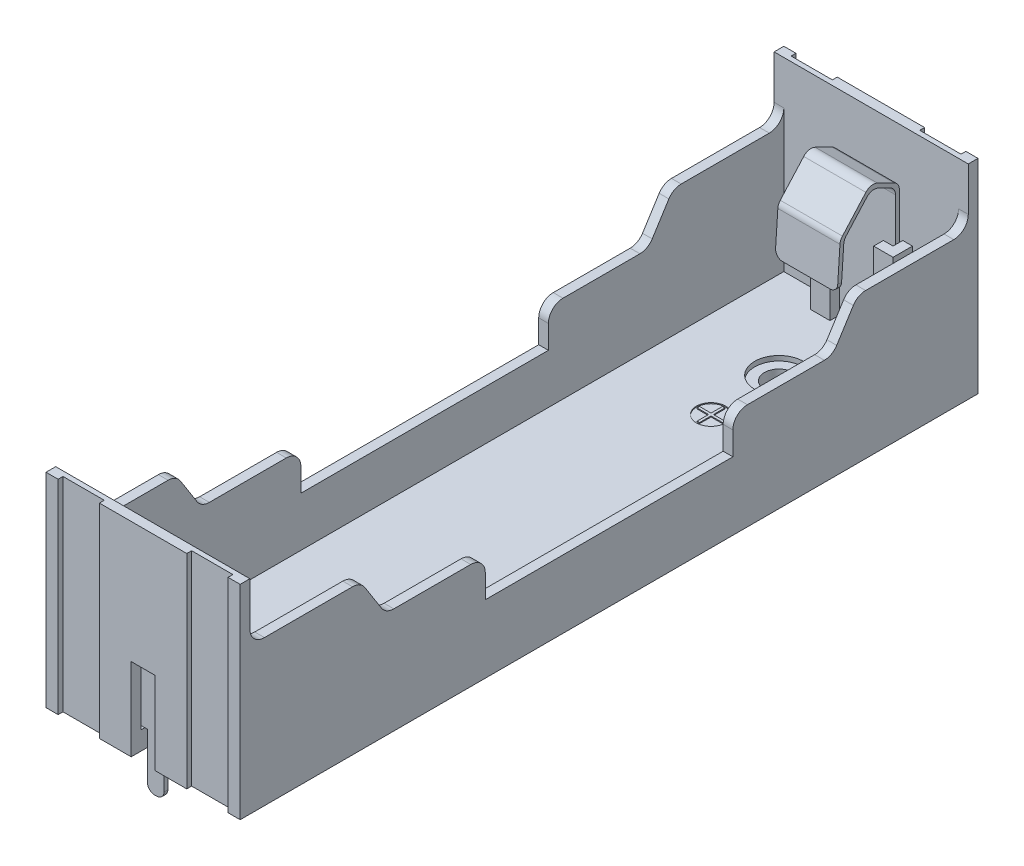
SolidWorks part; units mm, degrees
material "ABS"
ref_plane "Спереди" through (0, 0, 0) normal (0, 0, 1) x (1, 0, 0)
ref_plane "Сверху" through (0, 0, 0) normal (0, 1, 0) x (1, 0, 0)
ref_plane "Справа" through (0, 0, 0) normal (1, 0, 0) x (0, 0, -1)
other "Configuration Table"
sketch "Эскиз1" plane through (0, 0, 0) normal (0, 1, 0) x (1, 0, 0)
  line L1 (-10, 38) -> (10, 38)
  line L2 (-10, 38) -> (-10, -38)
  line L3 (-10, -38) -> (10, -38)
  line L4 (10, 38) -> (10, -38)
  line L5 (-10, 38) -> (10, -38) construction
  line L6 (-10, -38) -> (10, 38) construction
  point P0 (0, 0)
  dimension "D1" = 76
  dimension "D2" = 20
extrude "Основа" add sketch "Эскиз1" along normal blind 21
sketch "Эскиз2" plane through (0, 0, 0) normal (0, 1, 0) x (1, 0, 0)
  line L1 (10, 38) -> (-10, 38) construction
  line L2 (-4.5, 38) -> (-4.5, 37.5)
  line L3 (-4.5, 37.5) -> (-8.75, 37.5)
  line L4 (-8.75, 37.5) -> (-8.75, 38)
  line L5 (-8.75, 38) -> (-10.75, 38)
  line L6 (-10.75, 38) -> (-10.75, 37.5)
  line L13 (-10.75, 38) -> (-10, 38)
  line L14 (-10, 38) -> (-10, 46.5071)
  line L15 (-10, 46.5071) -> (10, 46.5071)
  line L16 (0, 46.5071) -> (0, 38)
  line L17 (4.5, 38) -> (-4.5, 38)
  line L18 (10, 38) -> (10, 46.5071)
  line L26 (10.75, 38) -> (10.75, 37.5)
  line L27 (8.75, 38) -> (10.75, 38)
  line L28 (4.5, 38) -> (4.5, 37.5)
  line L29 (4.5, 37.5) -> (8.75, 37.5)
  line L30 (8.75, 37.5) -> (8.75, 38)
  line L31 (10.75, 38) -> (10, 38)
  line L32 (-10.75, 37.5) -> (-8.75, 37.5)
  line L33 (10.75, 37.5) -> (8.75, 37.5)
  point P22 (0, 38)
  dimension "D1" = 9
  dimension "D2" = 2
  dimension "D3" = 4.25
  dimension "D4" = 0.5
extrude "Рёбра" cut sketch "Эскиз2" along normal through all contours L29 L30 L27 L26 L18 L15 L16 L17 L28 | L17 L16 L15 L14 L13 L6 L5 L4 L3 L2 region at (-5.0396, 0, -42.1438) region at (5.0396, 0, -42.1438)
mirror "Зеркальное отражение1" about plane through (0, 0, 0) normal (0, 0, 1) of "Рёбра"
sketch "Эскиз3" plane through (0, 21, 0) normal (0, 1, 0) x (1, 0, 0)
  line L0 (9, 0) -> (-9, 0) construction
  line L1 (9, 37) -> (-9, 37)
  line L2 (9, 37) -> (9, -37)
  line L3 (9, -37) -> (-9, -37)
  line L4 (-9, 37) -> (-9, -37)
  line L5 (9, 37) -> (-9, -37) construction
  line L6 (9, -37) -> (-9, 37) construction
  point P0 (0, 0)
  point P9 (0, 0)
  dimension "D1" = 18
  dimension "D2" = 74
extrude "Отсеки" cut sketch "Эскиз3" against normal blind 19.1
sketch "Эскиз4" plane through (0, 0, 0) normal (1, 0, 0) x (0, 0, -1)
  line L0 (37, 21) -> (-37, 21) construction
  line L1 (37, 27) -> (-37, 27)
  line L2 (37, 27) -> (37, 15)
  line L3 (37, 15) -> (-37, 15)
  line L4 (-37, 27) -> (-37, 15)
  line L5 (37, 27) -> (-37, 15) construction
  line L6 (37, 15) -> (-37, 27) construction
  line L7 (-37, 1.9) -> (-37, 21) construction
  point P0 (0, 21)
  dimension "D1" = 15
extrude "Уменьшение внутренних стенок" cut sketch "Эскиз4" against normal blind 15 and the other way blind 15
sketch "Эскиз5" plane through (10, 0, 0) normal (1, 0, 0) x (0, 0, -1)
  line L0 (-38, 21) -> (-35.6, 21)
  line L1 (-38, 21) -> (-37, 21) construction
  line L2 (-35.6, 21) -> (-35.6, 15)
  line L3 (-35.6, 15) -> (-25.6, 15)
  line L4 (-25.6, 15) -> (-23, 10.9)
  line L5 (-23, 10.9) -> (-12.75, 10.9)
  line L6 (-12.75, 10.9) -> (-12.75, 7)
  line L7 (-12.75, 7) -> (12.75, 7)
  line L8 (0, 7) -> (0, 0) construction
  line L9 (-35.6, 21) -> (35.6, 21)
  line L10 (12.75, 10.9) -> (12.75, 7)
  line L11 (23, 10.9) -> (12.75, 10.9)
  line L12 (25.6, 15) -> (23, 10.9)
  line L13 (35.6, 15) -> (25.6, 15)
  line L14 (35.6, 21) -> (35.6, 15)
  line L15 (-38, 21) -> (-37, 21) construction
  point P20 (0, 21)
  line M12 (38, 21) -> (37, 21)
  dimension "D1" = 12.75
  dimension "D2" = 10.25
  dimension "D3" = 2.4
  dimension "D4" = 10
  dimension "D5" = 6
  dimension "D6" = 3.9
  dimension "D7" = 7
extrude "Уменьшение внешних стенок" cut sketch "Эскиз5" against normal blind 15 contours L14 L2 L3 L4 L5 L6 L7 L10 L11 L12 L13 M12 region at (10, 15.384, 0)
fillet "Скругление2" radius 1.5 8 edges at (9.5, 10.9, -23) (9.5, 10.9, -12.75) (9.5, 10.9, 12.75) (9.5, 10.9, 23) (9.5, 15, -37) (9.5, 15, -25.6) (9.5, 15, 37) (9.5, 15, 25.6)
mirror "Зеркальное отражение2" about plane through (0, 0, 0) normal (1, 0, 0) of "Скругление2", "Уменьшение внешних стенок"
sketch "Эскиз6" plane through (0, 0, 0) normal (0, 1, 0) x (1, 0, 0)
  line L0 (-4.5, -38) -> (4.5, -38) construction
  line L1 (-1.225, -41.5) -> (1.225, -41.5)
  line L2 (-1.225, -41.5) -> (-1.225, -34.5)
  line L3 (-1.225, -34.5) -> (1.225, -34.5)
  line L4 (1.225, -41.5) -> (1.225, -34.5)
  line L5 (-1.225, -41.5) -> (1.225, -34.5) construction
  line L6 (-1.225, -34.5) -> (1.225, -41.5) construction
  line L7 (-10, 0) -> (10, 0) construction
  line L8 (10, -38) -> (10, 38) construction
  line L27 (-1.225, 34.5) -> (1.225, 41.5) construction
  line L28 (-1.225, 41.5) -> (1.225, 34.5) construction
  line L37 (1.225, 41.5) -> (1.225, 34.5)
  line L38 (-1.225, 34.5) -> (1.225, 34.5)
  line L39 (-1.225, 41.5) -> (-1.225, 34.5)
  line L40 (-1.225, 41.5) -> (1.225, 41.5)
  point P0 (0, -38)
  point P13 (0, 0)
  point P42 (0, 38)
  dimension "D1" = 2.45
  dimension "D2" = 3.5
extrude "Вырезы под контакты" cut sketch "Эскиз6" along normal blind 8.5
sketch "Эскиз11" plane through (0, 0, 0) normal (0, 1, 0) x (1, 0, 0)
  line L0 (0, 27.5) -> (0, -27.5) construction
  line L1 (1.5, -27.5) -> (-1.5, -27.5) construction
  line L3 (1.5, 27.5) -> (-1.5, 27.5) construction
  circle A1 centre (0, 27.5) radius 1.5
  circle A4 centre (0, -27.5) radius 1.5
  point P0 (0, 0)
  point P13 (0, 0)
  dimension "D2" = 3
  dimension "D1" = 55
extrude "Крепежные отверстия" cut sketch "Эскиз11" along normal through all
sketch "Эскиз12" plane through (0, 0, 0) normal (0, 1, 0) x (1, 0, 0)
  circle A1 centre (0, 27.5) radius 1.5 construction
  circle A4 centre (0, -27.5) radius 1.5 construction
  circle A7 centre (0, 27.5) radius 1.5
  circle A10 centre (0, -27.5) radius 1.5
  circle A13 centre (0, 27.5) radius 2.8
  circle A16 centre (0, -27.5) radius 2.8
  dimension "D1" = 1.3
extrude "Юбки отверстий" add sketch "Эскиз12" against normal blind 0.3
sketch "Эскиз13" plane through (0, 1.9, 0) normal (0, 1, 0) x (1, 0, 0)
  circle A1 centre (0, -27.5) radius 1.5 construction
  circle A3 centre (0, 27.5) radius 1.5 construction
  circle A6 centre (0, -27.5) radius 1.5
  circle A8 centre (0, 27.5) radius 1.5
  circle A13 centre (0, -27.5) radius 2.5
  circle A15 centre (0, 27.5) radius 2.5
  dimension "D1" = 1
extrude "Вырез-Вытянуть17" cut sketch "Эскиз13" against normal blind 0.5
sketch "Эскиз14" plane through (0, 1.9, 0) normal (0, 1, 0) x (1, 0, 0)
  line L0 (0, 20.5) -> (0, -20.5) construction
  line L3 (1.5, 20.5) -> (0, 20.5) construction
  line L4 (0, -20.5) -> (0, -19) construction
  line L5 (0, 19) -> (0, 20.5) construction
  line L8 (0.125, -19.2) -> (-0.125, -19.2)
  line L9 (0.125, -19.2) -> (0.125, -21.8)
  line L10 (0.125, -21.8) -> (-0.125, -21.8)
  line L11 (-0.125, -19.2) -> (-0.125, -21.8)
  line L12 (0.125, -19.2) -> (-0.125, -21.8) construction
  line L13 (0.125, -21.8) -> (-0.125, -19.2) construction
  line L14 (0.125, 21.8) -> (-0.125, 21.8)
  line L15 (0.125, 21.8) -> (0.125, 19.2)
  line L16 (0.125, 19.2) -> (-0.125, 19.2)
  line L17 (-0.125, 21.8) -> (-0.125, 19.2)
  line L18 (0.125, 21.8) -> (-0.125, 19.2) construction
  line L19 (0.125, 19.2) -> (-0.125, 21.8) construction
  line L20 (1.3, 20.625) -> (-1.3, 20.625)
  line L21 (1.3, 20.625) -> (1.3, 20.375)
  line L22 (1.3, 20.375) -> (-1.3, 20.375)
  line L23 (-1.3, 20.625) -> (-1.3, 20.375)
  line L24 (1.3, 20.625) -> (-1.3, 20.375) construction
  line L25 (1.3, 20.375) -> (-1.3, 20.625) construction
  circle A0 centre (0, 20.5) radius 1.5
  circle A1 centre (0, -20.5) radius 1.5
  point P0 (0, 0)
  point P2 (0, 0)
  dimension "D2" = 3
  dimension "D3" = 2.6
  dimension "D4" = 0.25
  dimension "D5" = 41
extrude "Полярность" cut sketch "Эскиз14" against normal blind 0.1 contours A1 L11 L8 L9 L10 | A0 L23 L20 L17 L14 L15 L21 L22 L16 region at (-1.4576, 1.9, -20.5) region at (-1.4576, 1.9, 20.5)
sketch "Эскиз15" plane through (0, 1.9, 0) normal (0, 1, 0) x (1, 0, 0)
  line L0 (-1.225, 37) -> (-9, 37) construction
  line L1 (-1.225, 37) -> (-1.225, 34.5) construction
  line L16 (-2.25, 35) -> (-4.25, 35)
  line L17 (-4.25, 35) -> (-4.25, 37)
  line L18 (-4.25, 37) -> (-3.25, 37)
  line L19 (-3.25, 37) -> (-3.25, 36)
  line L20 (-3.25, 36) -> (-2.25, 36)
  line L21 (-2.25, 36) -> (-2.25, 35)
  line L22 (2.25, 35) -> (2.25, 36)
  line L23 (2.25, 36) -> (3.25, 36)
  line L24 (3.25, 36) -> (3.25, 37)
  line L25 (3.25, 37) -> (4.25, 37)
  line L26 (4.25, 37) -> (4.25, 35)
  line L27 (4.25, 35) -> (2.25, 35)
  line L28 (0, 35.5) -> (0, 35) construction
  line L29 (-2.25, 35) -> (2.25, 35) construction
  line L44 (10, 0) -> (-10, 0) construction
  line L45 (-10, -12.75) -> (-10, 12.75) construction
  line L48 (-2.25, -35) -> (2.25, -35) construction
  line L49 (0, -35.5) -> (0, -35) construction
  line L64 (4.25, -35) -> (2.25, -35)
  line L65 (4.25, -37) -> (4.25, -35)
  line L66 (3.25, -37) -> (4.25, -37)
  line L67 (3.25, -36) -> (3.25, -37)
  line L68 (2.25, -36) -> (3.25, -36)
  line L69 (2.25, -35) -> (2.25, -36)
  line L70 (-2.25, -36) -> (-2.25, -35)
  line L71 (-3.25, -36) -> (-2.25, -36)
  line L72 (-3.25, -37) -> (-3.25, -36)
  line L73 (-4.25, -37) -> (-3.25, -37)
  line L74 (-4.25, -35) -> (-4.25, -37)
  line L75 (-2.25, -35) -> (-4.25, -35)
  point P4 (19.5, 35)
  point P24 (0, 35)
  point P55 (0, 0)
  point P99 (0, -35)
  dimension "D1" = 2
  dimension "D2" = 1.025
  dimension "D4" = 8.5
extrude "Пазы для контактов" add sketch "Эскиз15" along normal blind 8.9
ref_plane "Для эскиза контактов" through (0, 0, 0) normal (-1, 0, 0) x (0, 0, 1)
sketch "Эскиз16" plane through (0, 0, 0) normal (-1, 0, 0) x (0, 0, 1)
  line L1 (-38, 21) -> (-38, 0) construction
  line L3 (-36.5, 17.26) -> (-36.5, 15.9523) construction
  line L4 (-36.5, 15.9523) -> (-33.8, 17.26)
  line L5 (-33.8, 17.26) -> (-30.8, 13.9059)
  line L6 (-30.8, 13.9059) -> (-30.5, 9.4159)
  line L7 (-36.5, 17.26) -> (-33.8, 17.26) construction
  line L8 (-36.5, 15.9523) -> (-36.5, 2)
  line L10 (-36.5, 2) -> (-36.5, -3.54) construction
  line L12 (-38, 0) -> (38, 0) construction
  dimension "D1" = 20.8
  dimension "D2" = 3
  dimension "D3" = 4.5
  dimension "D4" = 6
  dimension "D5" = 5.7
  dimension "D6" = 2.7
  dimension "D7" = 2
  dimension "D8" = 1.5
  dimension "D9" = 13.9523
extrude "Контакт" add sketch "Эскиз16" along normal mid plane 6.4 thin thin type mid plane wall 0.4
sketch "Эскиз17" plane through (0, 2, 0) normal (0, -1, 0) x (1, 0, 0)
  line L0 (0, -36.7) -> (0, -36.3) construction
  line L1 (-3.2, -36.7) -> (3.2, -36.7) construction
  line L2 (-3.2, -36.3) -> (3.2, -36.3) construction
  line L4 (0.85, -36.3) -> (-0.85, -36.3)
  line L5 (0.85, -36.3) -> (0.85, -36.7)
  line L6 (0.85, -36.7) -> (-0.85, -36.7)
  line L7 (-0.85, -36.3) -> (-0.85, -36.7)
  line L8 (0.85, -36.3) -> (-0.85, -36.7) construction
  line L9 (0.85, -36.7) -> (-0.85, -36.3) construction
  point P6 (0, -36.5)
  dimension "D1" = 1.7
extrude "Штырёк для пайки" add sketch "Эскиз17" along normal blind 5.5
fillet "Скругление3" radius 1 6 edges at (0, 13.8239, -30.995) (0, 13.9879, -30.605) (0, 17.0143, -33.8485) (0, 17.5057, -33.7515) (0, 15.827, -36.3) (0, 16.0777, -36.7)
fillet "Скругление4" radius 0.75 6 edges at (3.2, 2, -36.5) (0.85, -3.5, -36.5) (-0.85, -3.5, -36.5) (-3.2, 2, -36.5) (3.2, 9.4159, -30.5) (-3.2, 9.4159, -30.5)
mirror "Mirror1" about plane through (0, 0, 0) normal (0, 0, 1) of bodies 125
equation "\"D1@Эскиз5\"=25.5/2"
